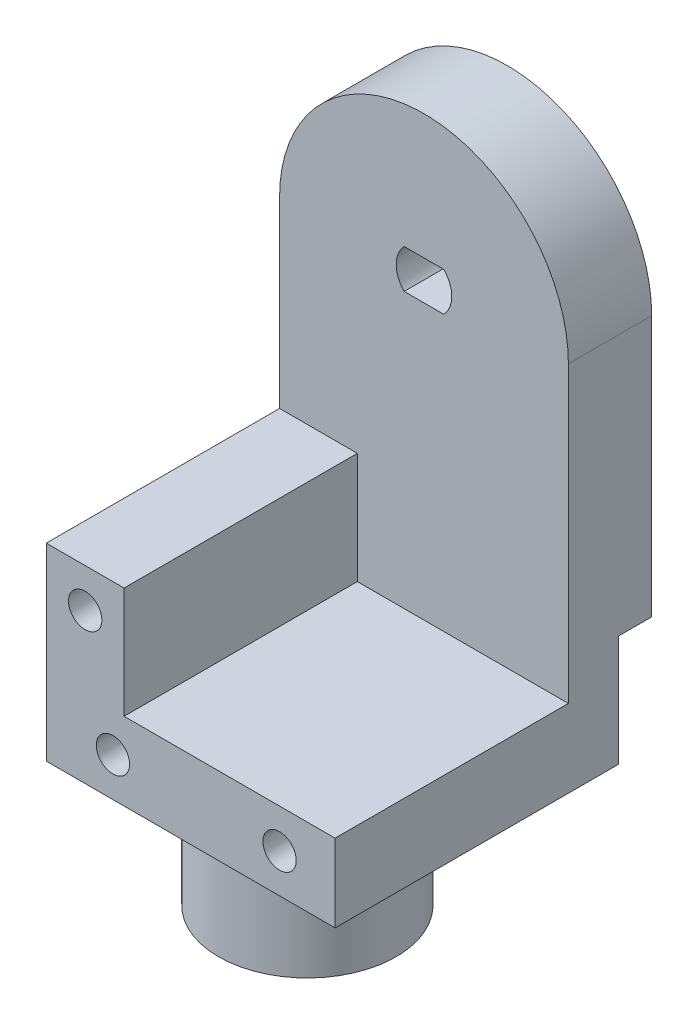
SolidWorks part; units mm, degrees
ref_plane "Front Plane" through (0, 0, 0) normal (0, 0, 1) x (1, 0, 0)
ref_plane "Top Plane" through (0, 0, 0) normal (0, 1, 0) x (1, 0, 0)
ref_plane "Right Plane" through (0, 0, 0) normal (1, 0, 0) x (0, 0, -1)
sketch "Sketch1" plane through (0, 0, 0) normal (0, 0, 1) x (1, 0, 0)
  line L7 (24.2641, -54) -> (50.2641, -54)
  line L9 (24.2641, -4) -> (50.2641, -4)
  line L10 (24.2641, -54) -> (24.2641, -4)
  line L11 (50.2641, -54) -> (50.2641, -4)
  line L14 (39.0495, -22.266) -> (35.4787, -22.266)
  line L15 (35.4787, -18.766) -> (39.0495, -18.766)
  line L16 (37.2641, -4) -> (37.2641, -54) construction
  arc A5 (35.4787, -18.766) -> (35.4787, -22.266) centre (37.2641, -20.516) ccw
  arc A6 (39.0495, -22.266) -> (39.0495, -18.766) centre (37.2641, -20.516) ccw
extrude "Boss-Extrude1" add sketch "Sketch1" along normal blind 8
sketch "Sketch2" plane through (0, 0, -20) normal (0, 0, -1) x (-1, 0, 0)
  line L0 (-39.0495, -18.766) -> (-35.4787, -18.766) construction
  line L1 (-35.4787, -22.266) -> (-39.0495, -22.266) construction
  line L2 (-39.0495, -18.766) -> (-35.4787, -18.766)
  line L3 (-35.4787, -22.266) -> (-39.0495, -22.266)
  line L4 (-50.2641, -4) -> (-50.2641, -54)
  line L5 (-24.2641, -4) -> (-50.2641, -4)
  line L6 (-24.2641, -4) -> (-50.2641, -4)
  line L7 (-50.2641, -4) -> (-50.2641, -54)
  line L9 (-50.2641, -54) -> (-24.2641, -54)
  line L10 (-24.2641, -54) -> (-24.2641, -4)
  line L16 (-50.2641, -54) -> (-24.2641, -54)
  line L17 (-24.2641, -54) -> (-24.2641, -4)
  arc A0 (-39.0495, -18.766) -> (-39.0495, -22.266) centre (-37.2641, -20.516) ccw construction
  arc A1 (-35.4787, -22.266) -> (-35.4787, -18.766) centre (-37.2641, -20.516) ccw construction
  arc A2 (-39.0495, -18.766) -> (-39.0495, -22.266) centre (-37.2641, -20.516) ccw
  arc A3 (-35.4787, -22.266) -> (-35.4787, -18.766) centre (-37.2641, -20.516) ccw
  dimension "D1" = 0
extrude "Boss-Extrude2" add sketch "Sketch2" along normal blind 8 separate body
sketch "Sketch3" plane through (0, 0, 8) normal (0, 0, 1) x (1, 0, 0)
  line L0 (24.2641, -54) -> (50.2641, -54) construction
  line L2 (24.2641, -54) -> (50.2641, -54)
  line L4 (24.2641, -47) -> (50.2641, -47)
  line L6 (50.2641, -47) -> (64.2641, -47) construction
  line L8 (24.2641, -54) -> (24.2641, -47)
  line L10 (50.2641, -54) -> (64.2641, -54) construction
  line L11 (50.2641, -54) -> (50.2641, -4) construction
  line L12 (50.2641, -54) -> (50.2641, -47)
  dimension "D1" = 7
extrude "Boss-Extrude3" add sketch "Sketch3" against normal up to surface (36 mm away) up to face at (37.2641, -29, -28)
sketch "Sketch4" plane through (0, -54, 0) normal (0, -1, 0) x (1, 0, 0)
  line L0 (24.2641, 8) -> (50.2641, 8) construction
  line L1 (37.2641, 8) -> (37.2641, -28) construction
  line L2 (24.2641, -28) -> (50.2641, -28) construction
  line L3 (37.2641, -10) -> (43.8453, -10) construction
  circle A0 centre (37.2641, -10) radius 8
  circle A1 centre (37.2641, -10) radius 5
extrude "Boss-Extrude4" add sketch "Sketch4" along normal blind 10
fillet "Fillet2" radius 3 2 edges at (24.2641, -29, 8) (24.2641, -29, -28)
sketch "Sketch6" plane through (0, 0, -20) normal (0, 0, 1) x (1, 0, 0)
  line L0 (27.2641, -54) -> (50.2641, -54) construction
  line L1 (24.2641, -37) -> (31.2641, -37)
  line L2 (24.2641, -37) -> (24.2641, -54)
  line L3 (24.2641, -54) -> (31.2641, -54)
  line L4 (31.2641, -37) -> (31.2641, -54)
extrude "Boss-Extrude5" add sketch "Sketch6" along normal up to surface (20 mm away) up to face at (37.2641, -25.5, 0)
chamfer "Chamfer1" distance 2 angle 45 1 edges at (37.2641, -54, -2)
sketch "Sketch7" plane through (0, 0, 0) normal (0, 0, -1) x (-1, 0, 0)
  line L6 (-50.2641, -4) -> (-50.2641, -47)
  line L7 (-50.2641, -4) -> (-50.2641, -47)
  line L8 (-50.2641, -47) -> (-31.2641, -47)
  line L9 (-31.2641, -47) -> (-31.2641, -37)
  line L10 (-31.2641, -37) -> (-24.2641, -37)
  line L11 (-31.2641, -37) -> (-24.2641, -37)
  line L12 (-24.2641, -37) -> (-24.2641, -4)
  line L15 (-50.2641, -47) -> (-31.2641, -47)
  line L16 (-31.2641, -47) -> (-31.2641, -37)
  line L21 (-24.2641, -37) -> (-24.2641, -4)
  line L22 (-24.2641, -4) -> (-50.2641, -4)
  line L23 (-24.2641, -4) -> (-50.2641, -4)
  dimension "D1" = 0
extrude "Cut-Extrude2" cut sketch "Sketch7" against normal blind 0.5
sketch "Sketch8" plane through (0, 0, -20) normal (0, 0, 1) x (1, 0, 0)
  line L6 (50.2641, -47) -> (50.2641, -4)
  line L7 (31.2641, -47) -> (50.2641, -47)
  line L8 (50.2641, -47) -> (50.2641, -4)
  line L10 (50.2641, -4) -> (24.2641, -4)
  line L11 (50.2641, -4) -> (24.2641, -4)
  line L12 (24.2641, -4) -> (24.2641, -37)
  line L13 (31.2641, -37) -> (31.2641, -47)
  line L14 (31.2641, -47) -> (50.2641, -47)
  line L20 (31.2641, -37) -> (31.2641, -47)
  line L21 (24.2641, -4) -> (24.2641, -37)
  line L22 (24.2641, -37) -> (31.2641, -37)
  line L23 (24.2641, -37) -> (31.2641, -37)
  dimension "D1" = 0
extrude "Cut-Extrude3" cut sketch "Sketch8" against normal blind 0.5
sketch "Sketch10" plane through (0, 0, 8) normal (0, 0, 1) x (1, 0, 0)
  line L0 (50.2641, -20.516) -> (50.2641, 2.2658)
  line L1 (50.2641, 2.2658) -> (24.2641, 2.2658)
  line L2 (24.2641, 2.2658) -> (24.2641, -20.516)
  arc A0 (50.2641, -20.516) -> (24.2641, -20.516) centre (37.2641, -20.516) ccw
extrude "Cut-Extrude4" cut sketch "Sketch10" against normal up to surface (36 mm away) up to face at (38.7641, -29, -28)
sketch "Sketch11" plane through (0, 0, 8) normal (0, 0, 1) x (1, 0, 0)
  line L0 (24.2641, -54) -> (24.2641, -20.516) construction
  line L1 (50.2641, -54) -> (24.2641, -54)
  line L2 (50.2641, -54) -> (50.2641, -44)
  line L3 (50.2641, -44) -> (24.2641, -44)
  line L4 (24.2641, -54) -> (24.2641, -44)
extrude "Cut-Extrude5" cut sketch "Sketch11" against normal blind 3
sketch "Sketch12" plane through (0, 0, -28) normal (0, 0, -1) x (-1, 0, 0)
  line L4 (-50.2641, -44) -> (-50.2641, -54)
  line L5 (-24.2641, -44) -> (-50.2641, -44)
  line L6 (-24.2641, -54) -> (-24.2641, -44)
  line L7 (-50.2641, -54) -> (-24.2641, -54)
  line L8 (-50.2641, -44) -> (-50.2641, -54)
  line L9 (-24.2641, -44) -> (-50.2641, -44)
  line L10 (-24.2641, -54) -> (-24.2641, -44)
  line L11 (-50.2641, -54) -> (-24.2641, -54)
  dimension "D1" = 0
extrude "Cut-Extrude6" cut sketch "Sketch12" against normal blind 3
sketch "Sketch13" plane through (0, 0, 8) normal (0, 0, 1) x (1, 0, 0)
  line L0 (31.2641, -37) -> (31.2641, -47) construction
  line L1 (31.2641, -37) -> (31.2641, -47) construction
  line L2 (31.2641, -37) -> (24.2641, -37) construction
  circle A0 centre (45.2641, -50.5) radius 1.5
  circle A1 centre (30.2641, -50.5) radius 1.5
  circle A2 centre (27.7641, -40.5) radius 1.5
extrude "Cut-Extrude7" cut sketch "Sketch13" against normal up to surface (36 mm away) up to face at (39.4931, -28.1629, -28)
sketch "Sketch14" plane through (0, 0, 8) normal (0, 0, 1) x (1, 0, 0)
  line L1 (52.1631, -6.1028) -> (22.4004, -6.1028)
  line L2 (52.1631, -6.1028) -> (52.1631, -65.4423)
  line L3 (52.1631, -65.4423) -> (22.4004, -65.4423)
  line L4 (22.4004, -6.1028) -> (22.4004, -65.4423)
extrude "Cut-Extrude8" cut sketch "Sketch14" against normal up to surface (7.5 mm away) up to face at (37.2641, -20.516, 0.5)
sketch "Sketch15" plane through (0, 0, -28) normal (0, 0, -1) x (-1, 0, 0)
  circle A0 centre (-27.7641, -40.5) radius 2.25
extrude "Cut-Extrude9" cut sketch "Sketch15" against normal blind 6
